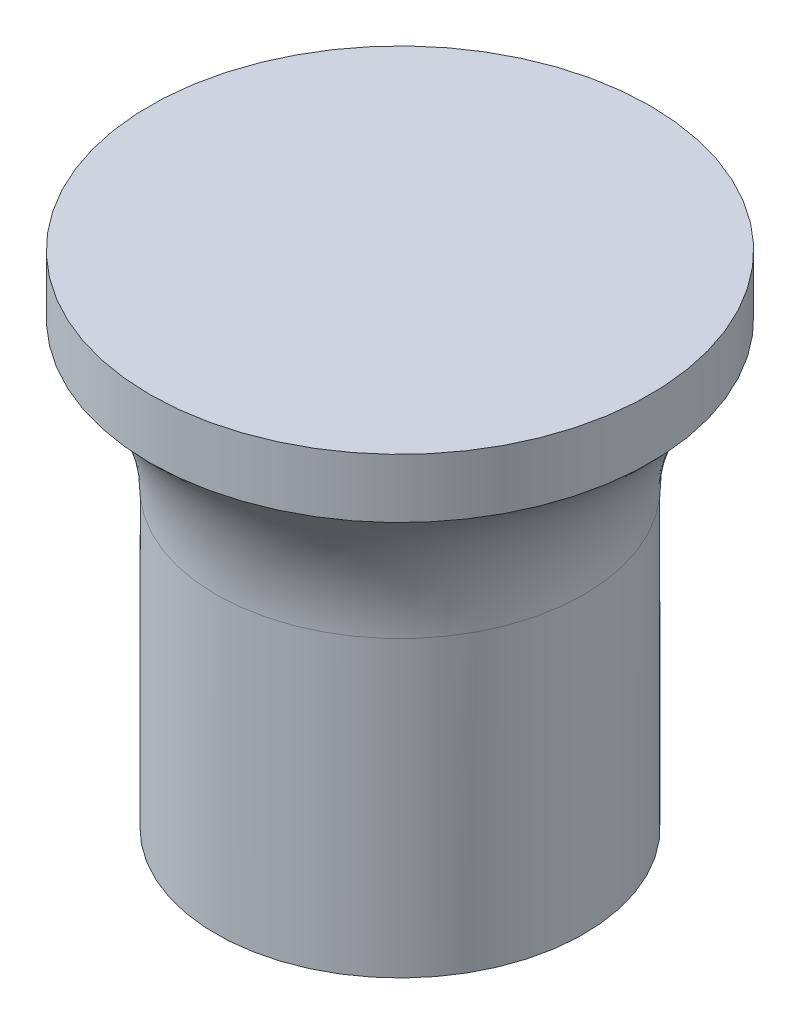
SolidWorks part; units mm, degrees
ref_plane "Front Plane" through (0, 0, 0) normal (0, 0, 1) x (1, 0, 0)
ref_plane "Top Plane" through (0, 0, 0) normal (0, 1, 0) x (1, 0, 0)
ref_plane "Right Plane" through (0, 0, 0) normal (1, 0, 0) x (0, 0, -1)
sketch "Sketch1" plane through (0, 0, 0) normal (0, 1, 0) x (1, 0, 0)
  circle A0 centre (0, 0) radius 12.7
  dimension "D1" = 25.4
extrude "Boss-Extrude1" add sketch "Sketch1" along normal blind 25.4
sketch "Sketch2" plane through (0, 0, 0) normal (0, -1, 0) x (1, 0, 0)
  circle A0 centre (0, 0) radius 6.34
  dimension "D1" = 12.68
extrude "Cut-Extrude1" cut sketch "Sketch2" against normal offset from surface (22.4 mm away) 3 up to face at (0, 25.4, 12.7)
sketch "Sketch3" plane through (0, 0, 0) normal (0, -1, 0) x (1, 0, 0)
  circle A0 centre (0, 0) radius 9.34
  circle A1 centre (0, 0) radius 12.7
  circle A2 centre (0, 0) radius 6.34 construction
  dimension "D1" = 3
extrude "Cut-Extrude4" cut sketch "Sketch3" against normal offset from surface (22.4 mm away) 3 up to face at (0, 25.4, 12.7)
fillet "Fillet1" radius 10 2 edges at (0, 0, -6.34) (0, 22.4, 9.34)
